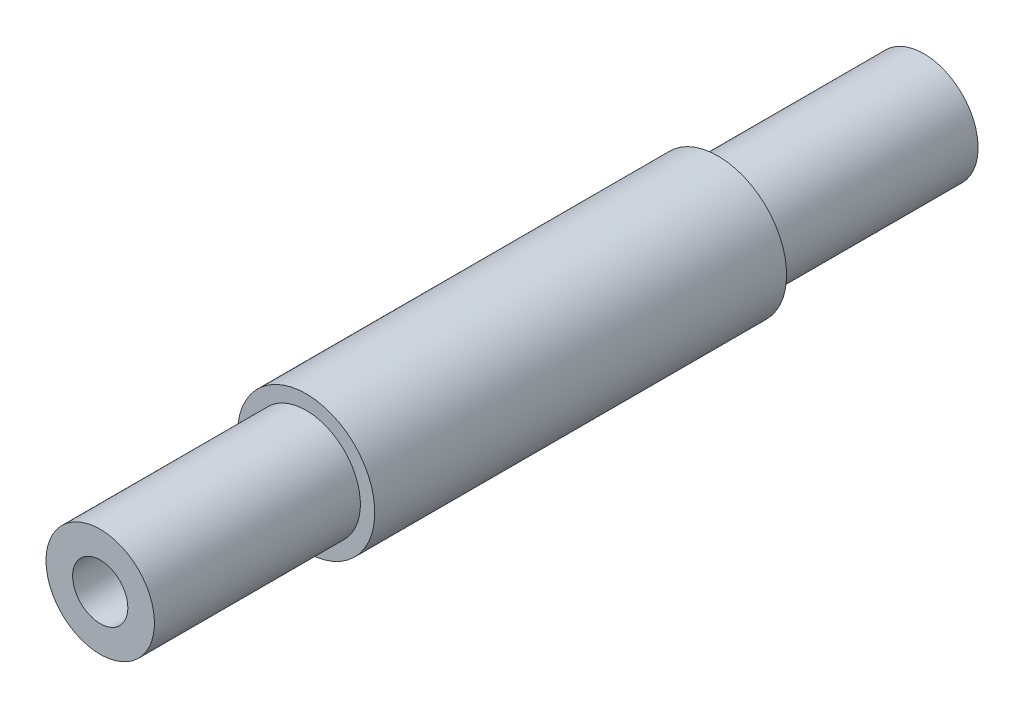
SolidWorks part; units mm, degrees
ref_plane "Front Plane" through (0, 0, 0) normal (0, 0, 1) x (1, 0, 0)
ref_plane "Top Plane" through (0, 0, 0) normal (0, 1, 0) x (1, 0, 0)
ref_plane "Right Plane" through (0, 0, 0) normal (1, 0, 0) x (0, 0, -1)
sketch "Sketch1" plane through (0, 0, 0) normal (0, 0, 1) x (1, 0, 0)
  circle A0 centre (0, 0) radius 6.35
  circle A1 centre (0, 0) radius 5.0165
  dimension "D1" = 12.7
  dimension "D2" = 10.033
extrude "Boss-Extrude1" add sketch "Sketch1" along normal mid plane 38.1 contours A1 | A0
extrude "Boss-Extrude2" add sketch "Sketch1<4>" along normal mid plane 76.2 contours A1 region at (0, 0, 0)
sketch "Sketch1<4>" plane through (0, 0, 0) normal (0, 0, 1) x (1, 0, 0) same geometry as "Sketch1"
hole_wizard "#7 (0.201) Diameter Hole1" positions "Sketch5" profile "Sketch6" hole size "#7" standard "ANSI Inch" end condition through all
sketch "Sketch5" plane through (0, 0, -38.1) normal (0, 0, -1) x (-1, 0, 0)
  point P0 (0, 0)
sketch "Sketch6" plane through (0, 0, -38.1) normal (1, 0, 0) x (0, 1, 0)
  line L0 (0, 0) -> (0, 76.2)
  line L1 (0, 76.2) -> (2.5527, 76.2)
  line L2 (2.5527, 76.2) -> (2.5527, 0)
  line L5 (2.5527, 0) -> (0, 0)
  line L11 (0, -6.35) -> (0, 107.95) construction
  dimension "Thru Hole Dia." = 5.1054
  dimension "Thru Hole Depth" = 76.2
cosmetic thread "Cosmetic Thread1" parameters "D2"=6.35
chamfer "Chamfer1" [suppressed] distance 0.254 angle 45
